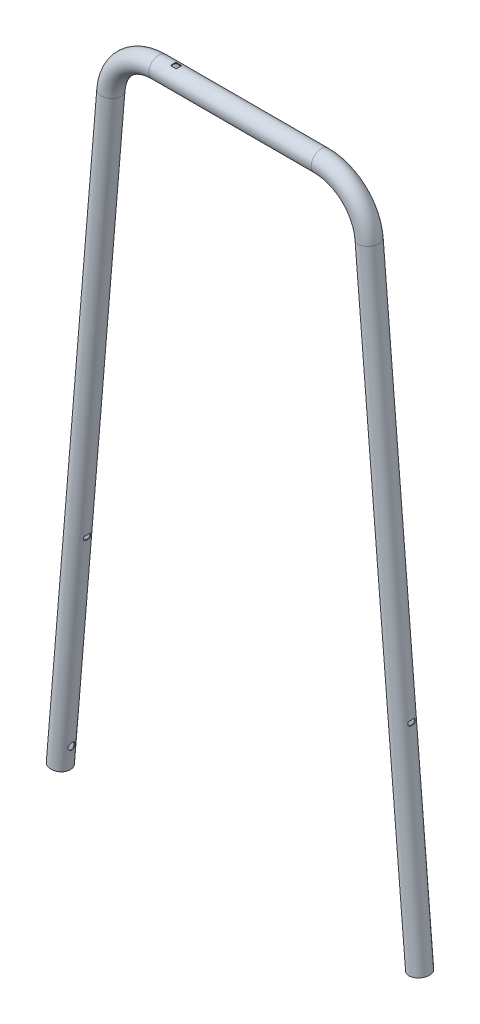
SolidWorks part; units mm, degrees
ref_plane "Front Plane" through (0, 0, 0) normal (0, 0, 1) x (1, 0, 0)
ref_plane "Top Plane" through (0, 0, 0) normal (0, 1, 0) x (1, 0, 0)
ref_plane "Right Plane" through (0, 0, 0) normal (1, 0, 0) x (0, 0, -1)
sketch "Sketch1" plane through (0, 0, 0) normal (0, 0, 1) x (1, 0, 0)
  line L0 (0, 0) -> (0, 595.2821) construction
  line L1 (0, 0) -> (414.971, 0) construction
  line L2 (-89.477, 556.716) -> (89.477, 556.716)
  line L3 (142.295, 508.1048) -> (198, -162.284)
  line L4 (-142.295, 508.1048) -> (-198, -162.284)
  line L5 (-198, -162.284) -> (-302.8448, -162.284) construction
  arc A0 (142.295, 508.1048) -> (89.477, 556.716) centre (89.477, 503.716) ccw
  arc A1 (-142.295, 508.1048) -> (-89.477, 556.716) centre (-89.477, 503.716) cw
  point P12 (138.2557, 556.716)
  point P17 (0, 556.716)
  dimension "D4" = 53
  dimension "D1" = 396
  dimension "D2" = 9.5
  dimension "D3" = 719
ref_plane "Plane1" through (-198, -162.284, 0) normal (-0.0828, -0.9966, 0) x (-0.9966, 0.0828, 0)
sketch "Sketch2" plane through (-198, -162.284, 0) normal (-0.0828, -0.9966, 0) x (-0.9966, 0.0828, 0)
  circle A0 centre (0, 0) radius 11
  circle A1 centre (0, 0) radius 10.2
  dimension "D1" = 0.8
sweep "Sweep2" add profiles "Sketch2" path "Sketch1"
sketch "Sketch6" plane through (-14.75, -177.5109, 0) normal (-0.0828, -0.9966, 0) x (0.9966, -0.0828, 0)
  line L0 (-183.8815, 0) -> (-194.0815, 0)
  line L1 (-183.8815, 0) -> (-183.8815, 10.2)
  circle A0 centre (-183.8815, 0) radius 10.2 construction
  circle A1 centre (-183.8815, 0) radius 10.2 construction
ref_plane "Plane3" through (-198, -162.284, 0) normal (-0.9966, 0.0828, 0) x (0, 0, 1)
ref_plane "Plane4" through (0, 567.716, 0) normal (0, 1, 0) x (1, 0, 0)
sketch "Sketch17" plane through (-198, -162.284, 0) normal (-0.9966, 0.0828, 0) x (0, 0, 1)
  line L0 (0, 0) -> (0, 23.5) construction
  line L1 (-11, 0) -> (11, 0) construction
  line L2 (0, 23.5) -> (0, 133.9257) construction
  circle A0 centre (0, 23.5) radius 4
  dimension "D3" = 8
  dimension "D1" = 23.5
  dimension "D2" = 133.9257
extrude "Cut-Extrude6" cut sketch "Sketch17" against normal blind 50
sketch "Sketch18" plane through (-198, -162.284, 0) normal (-0.9966, 0.0828, 0) x (0, 0, 1)
  line L0 (0, 0) -> (0, 232.5) construction
  line L1 (-10.2, 0) -> (10.2, 0) construction
  line L3 (-2, 235) -> (2, 235)
  line L4 (-4, 233) -> (-4, 232)
  line L5 (-2, 230) -> (2, 230)
  line L6 (4, 233) -> (4, 232)
  line L7 (-4, 235) -> (4, 230) construction
  line L8 (-4, 230) -> (4, 235) construction
  arc A0 (-2, 230) -> (-4, 232) centre (-2, 232) cw
  arc A1 (4, 232) -> (2, 230) centre (2, 232) cw
  arc A2 (2, 235) -> (4, 233) centre (2, 233) cw
  arc A3 (-2, 235) -> (-4, 233) centre (-2, 233) ccw
  dimension "D3" = 2
  dimension "D1" = 5
  dimension "D2" = 8
  dimension "D4" = 232.5
extrude "Cut-Extrude7" cut sketch "Sketch18" against normal blind 50 and the other way blind 50
mirror "Mirror2" about plane through (0, 0, 0) normal (1, 0, 0) of "Cut-Extrude6", "Cut-Extrude7"
sketch "Sketch19" plane through (-198, -162.284, 0) normal (-0.9966, 0.0828, 0) x (0, 0, 1)
  line L0 (0, 0) -> (0, 493.5) construction
  line L1 (-10.2, 0) -> (10.2, 0) construction
  circle A0 centre (0, 493.5) radius 4
  dimension "D1" = 493.5
extrude "Cut-Extrude8" cut sketch "Sketch19" along normal blind 50
sketch "Sketch20" plane through (0, 567.716, 0) normal (0, 1, 0) x (1, 0, 0)
  line L0 (-208.9622, 0) -> (-70.0622, 0) construction
  circle A0 centre (-70.0622, 0) radius 3.1
  ellipse E0 centre (-198, 0) end of major axis (-198, 11) minor radius 10.9622 construction
  dimension "D2" = 6.2
  dimension "D1" = 138.9
extrude "Cut-Extrude9" cut sketch "Sketch20" against normal blind 50
sketch "Sketch21" plane through (0, 567.716, 0) normal (0, 1, 0) x (1, 0, 0)
  line L0 (-208.9622, 0) -> (-70.0622, 0) construction
  line L2 (-72.3122, -3.1) -> (-67.8122, -3.1)
  line L3 (-73.3122, -2.1) -> (-73.3122, 2.1)
  line L4 (-72.3122, 3.1) -> (-67.8122, 3.1)
  line L5 (-66.8122, -2.1) -> (-66.8122, 2.1)
  line L6 (-73.3122, -3.1) -> (-66.8122, 3.1) construction
  line L7 (-73.3122, 3.1) -> (-66.8122, -3.1) construction
  arc A0 (-72.3122, 3.1) -> (-73.3122, 2.1) centre (-72.3122, 2.1) ccw
  arc A1 (-73.3122, -2.1) -> (-72.3122, -3.1) centre (-72.3122, -2.1) ccw
  arc A2 (-67.8122, 3.1) -> (-66.8122, 2.1) centre (-67.8122, 2.1) cw
  arc A3 (-66.8122, -2.1) -> (-67.8122, -3.1) centre (-67.8122, -2.1) cw
  ellipse E0 centre (-198, 0) end of major axis (-198, 11) minor radius 10.9622 construction
  dimension "D3" = 1
  dimension "D4" = 1
  dimension "D1" = 6.5
  dimension "D2" = 6.2
extrude "Cut-Extrude10" cut sketch "Sketch21" against normal blind 10
